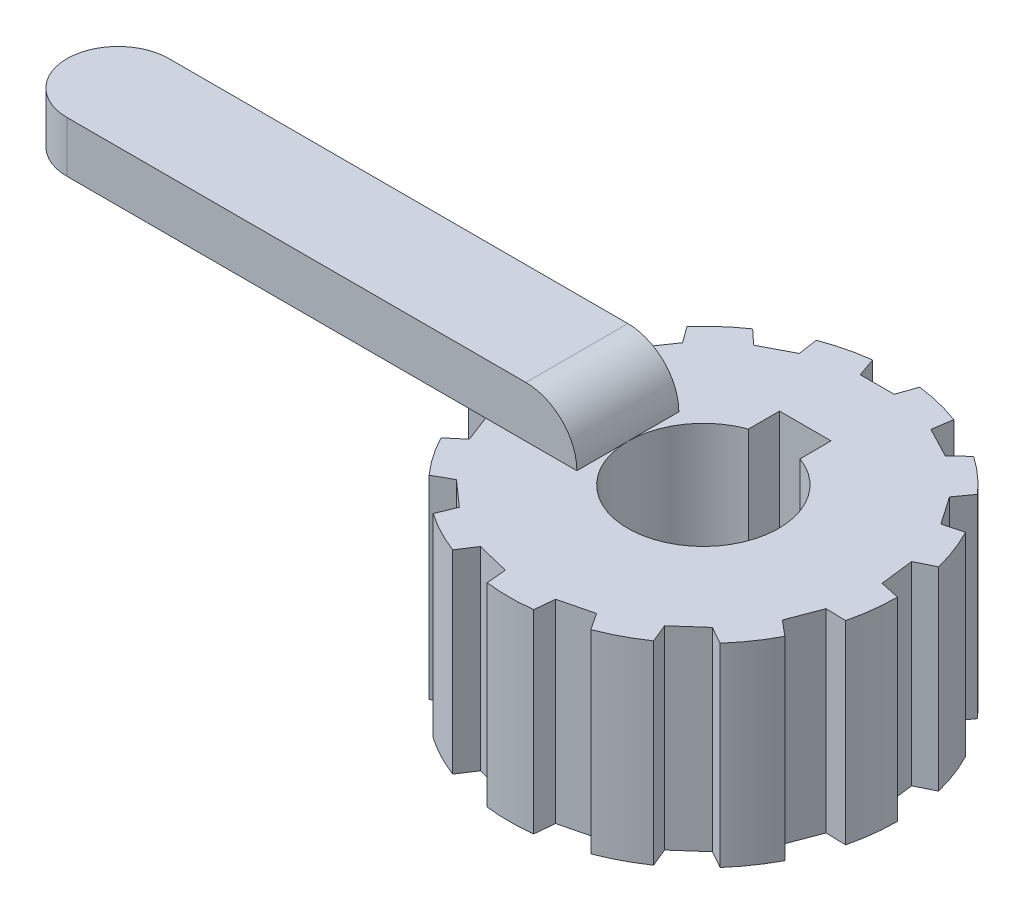
SolidWorks part; units mm, degrees
ref_plane "Front Plane" through (0, 0, 0) normal (0, 0, 1) x (1, 0, 0)
ref_plane "Top Plane" through (0, 0, 0) normal (0, 1, 0) x (1, 0, 0)
ref_plane "Right Plane" through (0, 0, 0) normal (1, 0, 0) x (0, 0, -1)
sketch "Sketch5" plane through (0, 0, 0) normal (0, 1, 0) x (1, 0, 0)
  circle A0 centre (0, 0) radius 19.05
extrude "Boss-Extrude2" add sketch "Sketch5" along normal blind 19.05
sketch "Sketch8" plane through (0, 19.05, 0) normal (0, 1, 0) x (1, 0, 0)
  line L0 (0, 19.05) -> (2.36, 19.05)
  line L1 (0, 19.05) -> (-2.36, 19.05)
  line L5 (0, 17.05) -> (-1.66, 17.05)
  line L6 (0, 17.05) -> (1.66, 17.05)
  line L7 (-2.36, 19.05) -> (-1.66, 17.05)
  line L8 (2.36, 19.05) -> (1.66, 17.05)
  circle A0 centre (0, 0) radius 19.05 construction
  point P0 (0, 19.05)
  dimension "D1" = 1.66
  dimension "D2" = 1.66
  dimension "D3" = 2
  dimension "D4" = 2.36
  dimension "D5" = 2.36
extrude "Cut-Extrude1" cut sketch "Sketch8" against normal blind 22.05
pattern_circular "CirPattern1" count 13 over 360 about axis through (0, 19.05, 0) along (0, 1, 0) of "Cut-Extrude1"
sketch "Sketch9" plane through (0, 19.05, 0) normal (0, 1, 0) x (1, 0, 0)
  line L0 (0, 7.4) -> (2.53, 7.4)
  line L1 (0, 7.4) -> (-2.53, 7.4)
  line L2 (-2.53, 7.4) -> (-2.53, 6.9541)
  line L3 (2.53, 7.4) -> (2.53, 6.9541)
  line L4 (-2.53, 7.4) -> (-2.53, 10)
  line L5 (-2.53, 10) -> (2.53, 10)
  line L6 (2.53, 10) -> (2.53, 7.4)
  circle A0 centre (0, 0) radius 7.4
  dimension "D1" = 2.53
  dimension "D2" = 2.53
  dimension "D3" = 2.6
extrude "Cut-Extrude2" cut sketch "Sketch9" against normal blind 25.4 contours A0 | L6 L5 L4 L1 L0 | A0 L1 L2 | A0 L3 L0 region at (0, 19.05, -8.7) region at (-1.9014, 19.05, -7.2669) region at (1.9014, 19.05, -7.2669) region at (0, 19.05, 0)
sketch "Sketch10" plane through (0, 19.05, 0) normal (0, 1, 0) x (1, 0, 0)
  line L7 (-7.4, 0) -> (-7.4, 5)
  line L8 (-7.4, 0) -> (-7.4, -5)
  line L9 (-7.4, 5) -> (-57.4, 5)
  line L10 (-57.4, 5) -> (-57.4, -5)
  line L11 (-57.4, -5) -> (-7.4, -5)
  arc A2 (-57.4, 5) -> (-57.4, -5) centre (-57.4, 0) ccw
  arc A3 (-2.53, 6.9541) -> (2.53, 6.9541) centre (0, 0) ccw construction
  dimension "D1" = 50
  dimension "D2" = 5
  dimension "D3" = 5
extrude "Boss-Extrude4" add sketch "Sketch10" along normal blind 5 contours L10 A2 | L10 L11 L8 L7 L9 region at (-32.4, 19.05, 0) region at (-59.5221, 19.05, 0)
fillet "Fillet2" radius 5 1 edges at (-7.4, 24.05, 0)
